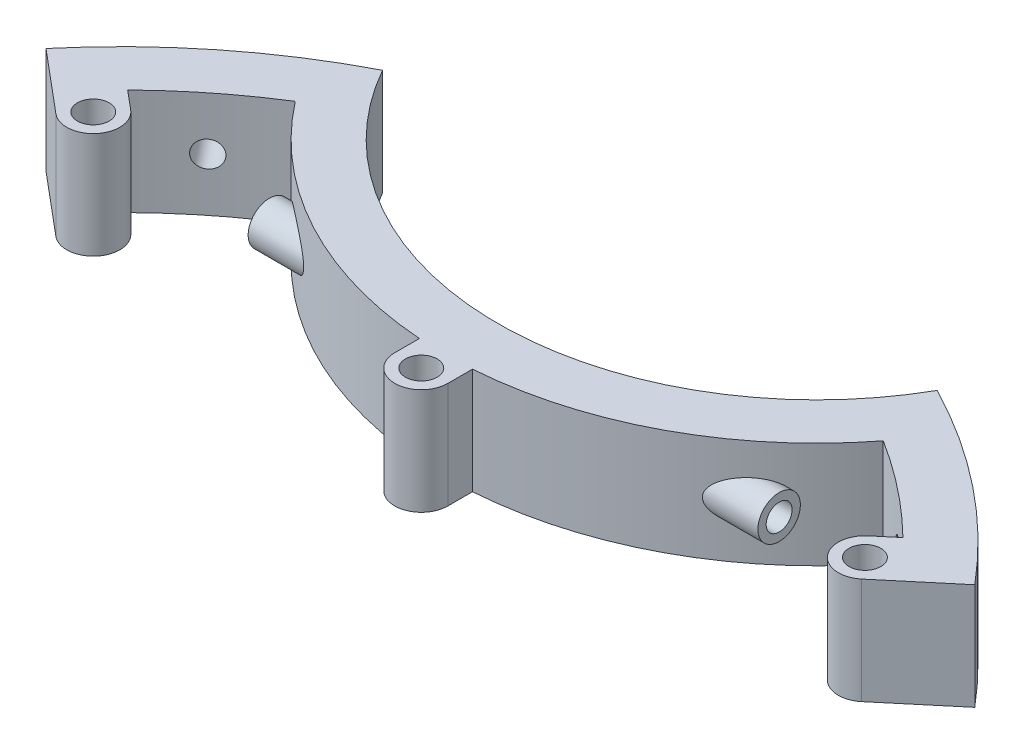
SolidWorks part; units mm, degrees
ref_plane "Front Plane" through (0, 0, 0) normal (0, 0, 1) x (1, 0, 0)
ref_plane "Top Plane" through (0, 0, 0) normal (0, 1, 0) x (1, 0, 0)
ref_plane "Right Plane" through (0, 0, 0) normal (1, 0, 0) x (0, 0, -1)
sketch "Sketch1" plane through (0, 0, 0) normal (0, 1, 0) x (1, 0, 0)
  line L0 (-33.1606, 64.4719) -> (0, 83.2333) construction
  line L1 (0, 83.2333) -> (33.1606, 64.4719) construction
  line L2 (-33.1606, 64.4719) -> (33.1606, 64.4719) construction
  line L3 (-55.5382, 46.6021) -> (-50.6738, 42.5204)
  line L4 (0, 0) -> (0, -18.8616) construction
  line L5 (55.5382, 46.6021) -> (50.6738, 42.5204)
  circle A0 centre (0, 0) radius 72.5
  circle A1 centre (0, 83.2333) radius 38.1
  arc A2 (-35.1569, 56.0341) -> (35.1569, 56.0341) centre (0, 0) ccw
  arc A3 (-35.1569, 56.0341) -> (35.1569, 56.0341) centre (0, 83.2333) ccw
  circle A4 centre (0, 0) radius 66.15 construction
  circle A5 centre (0, 83.2333) radius 44.45 construction
  point P12 (50.8, 83.2333)
  point P19 (-54.5437, 24.5158)
  point P20 (-59.7371, 41.082)
  dimension "D1" = 145
  dimension "D2" = 76.2
  dimension "D3" = 121
  dimension "D6" = 100
  dimension "D4" = 6.35
  dimension "D5" = 6.35
extrude "Boss-Extrude1" add sketch "Sketch1" along normal blind 12.7 contours A2 A3 L5 A0 A1 L3 region at (-44.5291, 0, -55.762)
sketch "Sketch3" plane through (0, 12.7, 0) normal (0, 1, 0) x (1, 0, 0)
  line L0 (-33.1606, 64.4719) -> (0, 0) construction
  line L1 (0, 0) -> (-55.5382, 46.6021) construction
  line L2 (0, 0) -> (-45.2405, 56.6529) construction
  arc A0 (-33.1606, 64.4719) -> (-55.5382, 46.6021) centre (0, 0) ccw construction
ref_plane "Plane1" through (-45.2405, 12.7, -56.6529) normal (-0.624, 0, -0.7814) x (-0.7814, 0, 0.624)
sketch "Sketch4" plane through (-45.2405, 12.7, -56.6529) normal (-0.624, 0, -0.7814) x (-0.7814, 0, 0.624)
  line L0 (-14.3186, -12.7) -> (14.3186, -12.7) construction
  circle A0 centre (0, -6.35) radius 1.55
  point P2 (0, -12.7)
  point P3 (0, 0)
  dimension "D1" = 3.1
  dimension "D2" = 6.35
extrude "Cut-Extrude1" cut sketch "Sketch4" against normal up to next
sketch "Sketch5" plane through (0, 12.7, 0) normal (0, 1, 0) x (1, 0, 0)
  line L0 (-48.1803, 40.4281) -> (-50.6738, 42.5204)
  line L1 (-55.5382, 46.6021) -> (-50.6738, 42.5204) construction
  line L2 (-44.0986, 45.2925) -> (-46.3581, 47.1884)
  arc A0 (-48.1803, 40.4281) -> (-44.0986, 45.2925) centre (-46.1394, 42.8603) ccw
  arc A1 (-35.1569, 56.0341) -> (-50.6738, 42.5204) centre (0, 0) ccw construction
  arc A2 (-46.3581, 47.1884) -> (-50.6738, 42.5204) centre (0, 0) ccw
  dimension "D1" = 6.35
extrude "Boss-Extrude2" add sketch "Sketch5" against normal blind 12.7
sketch "Sketch10" plane through (0, 12.7, 0) normal (0, 1, 0) x (1, 0, 0)
  line L0 (0, 38.7833) -> (0, 35.9472) construction
  line L1 (-3.175, 38.8968) -> (-3.175, 35.9472)
  line L2 (3.175, 35.9472) -> (3.175, 38.8968)
  line L3 (-44.0986, 45.2925) -> (-46.3581, 47.1884) construction
  line L7 (50.6738, 42.5204) -> (55.5382, 46.6021)
  line L8 (-55.5382, 46.6021) -> (-48.1803, 40.4281)
  line L9 (-44.0986, 45.2925) -> (-46.3581, 47.1884)
  arc A0 (-35.1569, 56.0341) -> (35.1569, 56.0341) centre (0, 83.2333) ccw construction
  arc A1 (-3.175, 35.9472) -> (3.175, 35.9472) centre (0, 35.9472) ccw
  arc A2 (-48.1803, 40.4281) -> (-44.0986, 45.2925) centre (-46.1394, 42.8603) ccw construction
  arc A10 (-35.1569, 56.0341) -> (-46.3581, 47.1884) centre (0, 0) ccw
  arc A11 (-35.1569, 56.0341) -> (35.1569, 56.0341) centre (0, 83.2333) ccw
  arc A12 (50.6738, 42.5204) -> (35.1569, 56.0341) centre (0, 0) ccw
  arc A13 (55.5382, 46.6021) -> (33.1606, 64.4719) centre (0, 0) ccw
  arc A14 (-33.1606, 64.4719) -> (33.1606, 64.4719) centre (0, 83.2333) ccw
  arc A15 (-33.1606, 64.4719) -> (-55.5382, 46.6021) centre (0, 0) ccw
  arc A16 (-48.1803, 40.4281) -> (-44.0986, 45.2925) centre (-46.1394, 42.8603) ccw
  arc A18 (-3.175, 38.8968) -> (3.175, 38.8968) centre (0, 83.2333) ccw
  point P14 (0, 36.3451)
  dimension "D1" = 0
extrude "Boss-Extrude4" add sketch "Sketch10" against normal blind 12.7
sketch "Sketch9" plane through (0, 0, 0) normal (1, 0, 0) x (0, 0, -1)
  circle A0 centre (48.26, 6.35) radius 2.54
  circle A1 centre (48.26, 6.35) radius 1.55
  point P5 (38.7833, 4.8764)
  point P6 (0, 0)
  point P7 (0, 0)
  point P8 (38.7833, 4.1453)
  point P9 (0, 0)
  point P10 (0, 0)
  point P11 (0, 0)
  dimension "D1" = 6.35
  dimension "D2" = 3.1
  dimension "D3" = 5.08
  dimension "D4" = 48.26
extrude "Cut-Extrude2" cut sketch "Sketch9" against normal up to next contours A1 region at (0, 6.35, -48.26)
extrude "Boss-Extrude3" add sketch "Sketch9<3>" against normal blind 7.62 from offset 22.86 contours A0 A1 region at (0, 6.35, -45.7918) offset against normal yes
sketch "Sketch9<3>" plane through (0, 0, 0) normal (1, 0, 0) x (0, 0, -1) same geometry as "Sketch9"
mirror "Mirror1" about plane through (0, 0, 0) normal (1, 0, 0) of "Boss-Extrude3", "Cut-Extrude2", "Cut-Extrude1", "Boss-Extrude2"
hole_wizard "#6 Clearance Hole1" positions "Sketch8" profile "Sketch7" hole size "#6" standard "ANSI Inch" end condition through all
sketch "Sketch8" plane through (0, 12.7, 0) normal (0, 1, 0) x (1, 0, 0)
  point P0 (-46.1394, 42.8603)
  point P3 (46.1394, 42.8603)
  point P7 (0, 35.9472)
sketch "Sketch7" plane through (-46.1394, 12.7, -42.8603) normal (1, 0, 0) x (0, 0, 1)
  line L0 (0, 0) -> (0, 12.7)
  line L1 (0, 12.7) -> (1.8986, 12.7)
  line L2 (1.8986, 12.7) -> (1.8986, 0)
  line L5 (1.8986, 0) -> (0, 0)
  line L11 (0, -6.35) -> (0, 107.95) construction
  dimension "Thru Hole Dia." = 3.7973
  dimension "Thru Hole Depth" = 12.7
